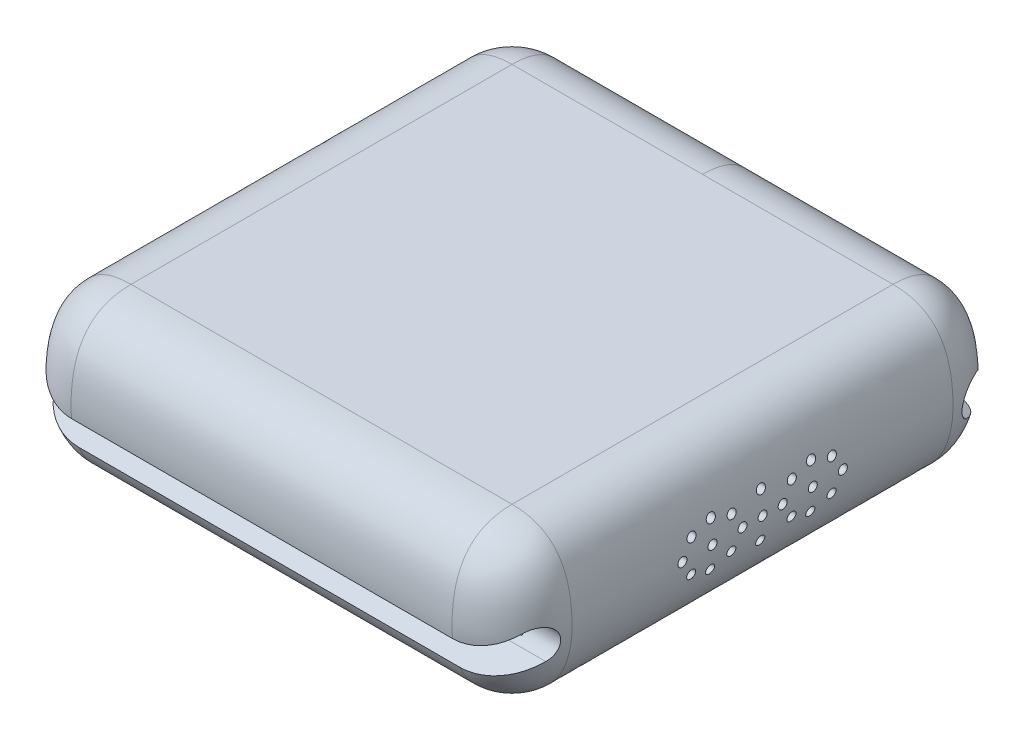
SolidWorks part; units mm, degrees
ref_plane "Alzado" through (0, 0, 0) normal (0, 0, 1) x (1, 0, 0)
ref_plane "Planta" through (0, 0, 0) normal (0, 1, 0) x (1, 0, 0)
ref_plane "Vista lateral" through (0, 0, 0) normal (1, 0, 0) x (0, 0, -1)
sketch "Croquis2" plane through (0, 0, 0) normal (0, 1, 0) x (1, 0, 0)
  line L1 (25, -25) -> (-25, -25)
  line L2 (25, -25) -> (25, 25)
  line L3 (25, 25) -> (-25, 25)
  line L4 (-25, -25) -> (-25, 25)
  line L5 (25, -25) -> (-25, 25) construction
  line L6 (25, 25) -> (-25, -25) construction
  point P0 (0, 0)
  dimension "D1" = 50
  dimension "D2" = 50
extrude "Saliente-Extruir1" add sketch "Croquis2" along normal mid plane 15
fillet "Redondeo2" radius 6 1 edges at (-25, 0, -25)
fillet "Redondeo3" radius 6 3 edges at (-25, 0, 25) (25, 0, 25) (25, 0, -25)
sketch "Croquis8" plane through (0, 0, 0) normal (1, 0, 0) x (0, 0, -1)
  line L0 (25, 7.5) -> (25, -7.5) construction
  line L1 (18.1307, 7.5) -> (10.8522, 7.5) construction
  line L2 (11.7402, -7.5) -> (17.2616, -7.5) construction
  line L3 (25, -2.5896) -> (25, 2.6882) construction
  line L4 (19, -7.5) -> (25, -7.5) construction
  line L5 (25, 7.5) -> (19, 7.5) construction
  line L6 (19, -7.5) -> (26.5483, -7.5)
  line L7 (25, 7.5) -> (25, -7.5) construction
  line L8 (26.5483, 7.5) -> (19, 7.5)
  line L9 (26.5483, 7.5) -> (26.5483, -7.5)
  spline S0 degree 3 poles (19, 7.5) (24.145, 7.5) (24.9796, 2.4061) (25.0396, -2.4061) (23.545, -7.5) (19, -7.5) knots 0 0 0 0 0.45 0.55 1 1 1 1
  dimension "D1" = 17.15
  dimension "D2" = 15.65
  dimension "D3" = 15.15
sketch "Croquis23" plane through (0, 0, 0) normal (0, 1, 0) x (1, 0, 0)
  line L0 (25, 19) -> (25, -19)
  line L1 (25, 19) -> (25, -19)
  line L2 (19, -25) -> (-19, -25)
  line L3 (19, -25) -> (-19, -25)
  line L4 (-25, -19) -> (-25, 19)
  line L5 (-25, -19) -> (-25, 19)
  line L6 (-19, 25) -> (19, 25)
  line L7 (-19, 25) -> (19, 25)
  arc A0 (19, -25) -> (25, -19) centre (19, -19) ccw
  arc A1 (19, -25) -> (25, -19) centre (19, -19) ccw
  arc A2 (-25, -19) -> (-19, -25) centre (-19, -19) ccw
  arc A3 (-25, -19) -> (-19, -25) centre (-19, -19) ccw
  arc A4 (-19, 25) -> (-25, 19) centre (-19, 19) ccw
  arc A5 (-19, 25) -> (-25, 19) centre (-19, 19) ccw
  arc A6 (25, 19) -> (19, 25) centre (19, 19) ccw
  arc A7 (25, 19) -> (19, 25) centre (19, 19) ccw
sweep "Cortar-Barrer11" cut profiles "Croquis8" path "Croquis23"
sketch "Croquis26" plane through (0, 0, 0) normal (1, 0, 0) x (0, 0, -1)
  line L0 (-19, 7.5) -> (-19, -7.5) construction
  line L1 (-19, 7.5) -> (-19, -7.5) construction
  line L2 (19, -7.5) -> (-19, -7.5) construction
  line L3 (-19, 0) -> (-11.75, 0) construction
  line L4 (-11.75, 0) -> (0, 0) construction
  line L5 (-2, 0) -> (-4, 0) construction
  line L10 (7.25, -3.25) -> (-7.25, 3.25) construction
  line L11 (7.25, 3.25) -> (-7.25, -3.25) construction
  line L12 (-7.25, 0) -> (0, 0) construction
  line L13 (7.25, 0) -> (0, 0) construction
  line L14 (0, 0) -> (0, 3.25) construction
  line L15 (0, 1.625) -> (-7.25, 1.625) construction
  line L16 (0, 1.625) -> (7.25, 1.625) construction
  line L17 (0, 0) -> (0, -3.25) construction
  line L18 (0, -1.625) -> (-7.25, -1.625) construction
  line L19 (0, -1.625) -> (7.25, -1.625) construction
  line L20 (-3.625, -1.625) -> (0, 0) construction
  line L21 (0, 0) -> (3.625, 0) construction
  line L22 (3.625, 0) -> (1.8125, 0) construction
  line L23 (2, 0) -> (4, 0) construction
  line L24 (-4, 0) -> (-6, 0) construction
  line L25 (0, 0) -> (-2, 0) construction
  line L26 (-2, 0) -> (-1, 0) construction
  line L27 (4, 0) -> (6, 0) construction
  line L28 (-4, 0) -> (-6, 0)
  line L29 (0, 0) -> (2, 0) construction
  line L30 (0, 0) -> (2, 0.8966) construction
  line L31 (0, 0) -> (-2, 0.8966) construction
  line L32 (-6, 0) -> (-5, 0)
  line L33 (-5, 0) -> (-5, 2.2414)
  line L34 (-4, 0) -> (-2, 0)
  line L35 (-2, 0) -> (-3, 0)
  line L36 (-3, 0) -> (-3, 1.625)
  line L37 (-2, 0) -> (0, 0)
  line L38 (0, 0) -> (-1, 0)
  line L39 (-1, 0) -> (-1, 1.625)
  line L40 (-1, 1.625) -> (-1, 0.8125)
  line L41 (0, 0) -> (2, 0)
  line L42 (2, 0) -> (1, 0)
  line L43 (1, 0) -> (1, 1.625)
  line L44 (1, 1.625) -> (1, 0.8125)
  line L45 (2, 0) -> (4, 0)
  line L46 (4, 0) -> (3, 0)
  line L47 (3, 0) -> (3, 1.625)
  line L48 (4, 0) -> (6, 0)
  line L49 (6, 0) -> (5, 0)
  line L50 (5, 0) -> (5, 2.2414)
  line L51 (-5, 0) -> (-5, -2.2414)
  line L52 (-3, 0) -> (-3, -1.625)
  line L53 (-1, 0) -> (-1, -1.625)
  line L54 (-1, -1.625) -> (-1, -0.8125)
  line L55 (1, 0) -> (1, -1.625)
  line L56 (1, -1.625) -> (1, -0.8125)
  line L57 (3, 0) -> (3, -1.625)
  line L58 (5, 0) -> (5, -2.2414)
  line L59 (-5, 2.2414) -> (5, 2.2414) construction
  line L60 (-5, -2.2414) -> (5, -2.2414) construction
  line L61 (-5, 0) -> (-8, 0) construction
  line L62 (-3, 1.625) -> (-7, 1.625) construction
  line L63 (-3, -1.625) -> (-7, -1.625) construction
  line L64 (-7, 0) -> (-8, 0) construction
  line L65 (3, 1.625) -> (7, 1.625) construction
  line L66 (3, -1.625) -> (7, -1.625) construction
  line L67 (5, 0) -> (8, 0) construction
  circle A2 centre (-2, 0) radius 0.45
  circle A3 centre (0, 0) radius 0.45
  circle A4 centre (2, 0) radius 0.45
  circle A7 centre (-5, 2.2414) radius 0.45
  circle A8 centre (-3, 1.625) radius 0.45
  circle A12 centre (3, 1.625) radius 0.45
  circle A13 centre (5, 2.2414) radius 0.45
  circle A14 centre (-5, -2.2414) radius 0.45
  circle A15 centre (-3, -1.625) radius 0.45
  circle A18 centre (3, -1.625) radius 0.45
  circle A19 centre (5, -2.2414) radius 0.45
  circle A20 centre (0, 2.2414) radius 0.45
  circle A21 centre (0, -2.2414) radius 0.45
  circle A22 centre (5, 0) radius 0.45
  circle A23 centre (-5, 0) radius 0.45
  circle A25 centre (-7, 1.625) radius 0.45
  circle A26 centre (-7, -1.625) radius 0.45
  circle A27 centre (-8, 0) radius 0.45
  circle A28 centre (7, 1.625) radius 0.45
  circle A29 centre (7, -1.625) radius 0.45
  circle A30 centre (8, 0) radius 0.45
  dimension "D5" = 2
  dimension "D10" = 0.9
  dimension "D11" = 0.9
  dimension "D12" = 0.9
  dimension "D13" = 0.9
  dimension "D14" = 0.9
  dimension "D15" = 3
  dimension "D16" = 0.9
  dimension "D17" = 0.9
  dimension "D18" = 0.9
  dimension "D19" = 4
  dimension "D20" = 0.9
  dimension "D21" = 4
  dimension "D22" = 0.9
  dimension "D23" = 0.9
  dimension "D24" = 0.9
  dimension "D25" = 0.9
  dimension "D26" = 0.9
  dimension "D27" = 1
  dimension "D28" = 0.9
  dimension "D35" = 3.4118
  dimension "D42" = 0.9
  dimension "D43" = 0.9
  dimension "D44" = 0.9
  dimension "D47" = 0.9
  dimension "D49" = 0.9
  dimension "D50" = 0.9
  dimension "D1" = 7.25
  dimension "D2" = 14.5
  dimension "D3" = 6.5
  dimension "D4" = 2
  dimension "D6" = 2
  dimension "D7" = 2
  dimension "D8" = 2
  dimension "D9" = 2
  dimension "D29" = 2
  dimension "D30" = 2
  dimension "D31" = 14.5
  dimension "D32" = 7.25
  dimension "D33" = 7.25
  dimension "D34" = 4.4828
  dimension "D36" = 5.4794
  dimension "D37" = 3.4118
  dimension "D38" = 7.25
  dimension "D39" = 7.25
  dimension "D40" = 14.5
  dimension "D41" = 7.25
  dimension "D45" = 4
  dimension "D46" = 4
  dimension "D48" = 3
extrude "Cortar-Extruir1" cut sketch "Croquis26" against normal through all both and the other way through all contours A8 | A23 | A14 | A15 | A2 | A3 | A4 | A18 | A19 | A22 | A12 | A13 | A7 | A20 | A21 | A25 | A27 | A26 | A28 | A30 | A29
sketch "Croquis41" plane through (0, 0, 0) normal (1, 0, 0) x (0, 0, -1)
  line L0 (0, -7) -> (0, -9.94)
  line L1 (-13.3, -7) -> (-13.3, -7.8)
  line L2 (19, -7.5) -> (-19, -7.5) construction
  line L3 (-13.3, -7.8) -> (-12.76, -8.34)
  line L4 (0, -9.94) -> (8.0573, -9.94) construction
  line L5 (19, -7.5) -> (-19, -7.5)
  line L6 (0, -7.5) -> (-13.3, -7.5) construction
  line L7 (19, 7.5) -> (-19, 7.5) construction
  line L8 (-13.3, -7) -> (0, -7)
  arc A0 (-12.76, -8.34) -> (0, -9.94) centre (0, 41.7405) ccw
  dimension "D1" = 17.44
  dimension "D2" = 13.3
  dimension "D3" = 0.5
  dimension "D4" = 135
  dimension "D5" = 15.84
  dimension "D6" = 0.3
revolve "Revolución1" add sketch "Croquis41" angle 360 about L0 other way angle 360
sketch "Croquis42" plane through (0, 0, 0) normal (1, 0, 0) x (0, 0, -1)
  line L0 (0, 0) -> (-23.1292, 0) construction
  line L1 (-20.26, 0) -> (-28.6396, -5.035) construction
  line L2 (-27.4089, -2.9538) -> (-22.7314, 0.4896)
  line L3 (-22.7314, 0.4896) -> (-21.7236, -0.8794) construction
  line L4 (-27.4089, -2.9538) -> (-26.2243, -4.9253)
  line L5 (-26.2243, -4.9253) -> (-20.988, -2.412)
  arc A0 (-22.7314, 0.4896) -> (-20.988, -2.412) centre (-21.7236, -0.8794) cw
  point P12 (-26.8166, -3.9396)
  dimension "D3" = 5.36
  dimension "D4" = 1.7
  dimension "D1" = 31
  dimension "D2" = 20.26
  dimension "D5" = 1.7
  dimension "D6" = 2.3
extrude "Cortar-Extruir2" cut sketch "Croquis42" against normal through all both and the other way through all
mirror "Simetría5" about plane through (0, 0, 0) normal (0, 0, 1) of "Cortar-Extruir2"
sketch "Croquis51" plane through (0, 0, 0) normal (0, 1, 0) x (1, 0, 0)
  line L2 (0, 0) -> (-24.8895, 0) construction
  line L12 (0, 0) -> (24.8895, 0) construction
  line L13 (-24.8895, 0) -> (-21.3895, 0) construction
  line L14 (24.8895, 0) -> (21.3895, 0) construction
  line L15 (21.3895, 20.4) -> (21.3895, 23.9) construction
  line L16 (-21.3895, 0) -> (-21.3895, 23.9) construction
  line L17 (-21.3895, 23.9) -> (-21.3895, 20.4) construction
  line L19 (-21.3895, 0) -> (-21.3895, -23.9) construction
  line L21 (-21.3895, -23.9) -> (-21.3895, -20.4) construction
  line L22 (21.3895, 0) -> (21.3895, 20.4) construction
  line L23 (21.3895, 0) -> (21.3895, -20.4) construction
  line L24 (21.3895, -20.4) -> (21.3895, -23.9) construction
  line L25 (-21.3895, 20.4) -> (21.3895, 20.4) construction
  line L26 (-21.3895, -20.4) -> (21.3895, -20.4) construction
  line L27 (21.3895, 20.4) -> (21.3895, -20.4)
  line L28 (21.3895, -20.4) -> (-21.3895, -20.4)
  line L29 (-21.3895, -20.4) -> (-21.3895, 20.4)
  line L30 (-21.3895, 20.4) -> (21.3895, 20.4)
  spline S2 degree 3 poles (-24.8101, 0.45) (-24.8466, 0.45) (-24.8625, 0.4017) (-24.8839, 0.2352) (-24.8895, 0.1177) (-24.8894, -0.1207) (-24.8837, -0.2379) (-24.8622, -0.4029) (-24.8461, -0.4505) (-24.81, -0.4495) (-24.79, -0.4019) (-24.7591, -0.2342) (-24.7494, -0.1168) (-24.7495, 0.1193) (-24.7595, 0.237) (-24.7901, 0.4021) (-24.8101, 0.45) (-24.8466, 0.45) (-24.8625, 0.4017) knots -0.125 -0.125 0 0 0.125 0.125 0.25 0.25 0.375 0.375 0.5 0.5 0.625 0.625 0.75 0.75 0.875 0.875 1 1 1.125 1.125 1.25 only from (-24.8284, 0.45) to (-24.8284, 0.45) construction
  spline S4 degree 3 poles (24.8466, 0.45) (24.8101, 0.45) (24.7901, 0.4019) (24.7595, 0.2367) (24.7495, 0.1196) (24.7495, -0.119) (24.7594, -0.236) (24.7899, -0.4012) (24.81, -0.4496) (24.8462, -0.4504) (24.8622, -0.4036) (24.8839, -0.236) (24.8895, -0.1187) (24.8895, 0.1175) (24.8839, 0.2356) (24.8625, 0.4018) (24.8466, 0.45) (24.8101, 0.45) (24.7901, 0.4019) knots -0.125 -0.125 0 0 0.125 0.125 0.25 0.25 0.375 0.375 0.5 0.5 0.625 0.625 0.75 0.75 0.875 0.875 1 1 1.125 1.125 1.25 only from (24.8284, 0.45) to (24.8284, 0.45) construction
  dimension "D1" = 3.5
  dimension "D2" = 3.5
  dimension "D3" = 3.5
  dimension "D4" = 3.5
  dimension "D5" = 3.5
  dimension "D6" = 3.5
  dimension "D7" = 20.4
  dimension "D8" = 20.4
extrude "Cortar-Extruir3" cut sketch "Croquis51" against normal mid plane 10
sketch "Croquis52" plane through (0, -5, 0) normal (0, 1, 0) x (1, 0, 0)
  circle A0 centre (0, 0) radius 10
  dimension "D1" = 20
extrude "Cortar-Extruir5" cut sketch "Croquis52" against normal blind 4
ref_plane "Plano2" through (24.3641, -2.412, 20.988) normal (-0.4034, -0.3959, 0.8249) x (0.915, -0.1746, 0.3637)
